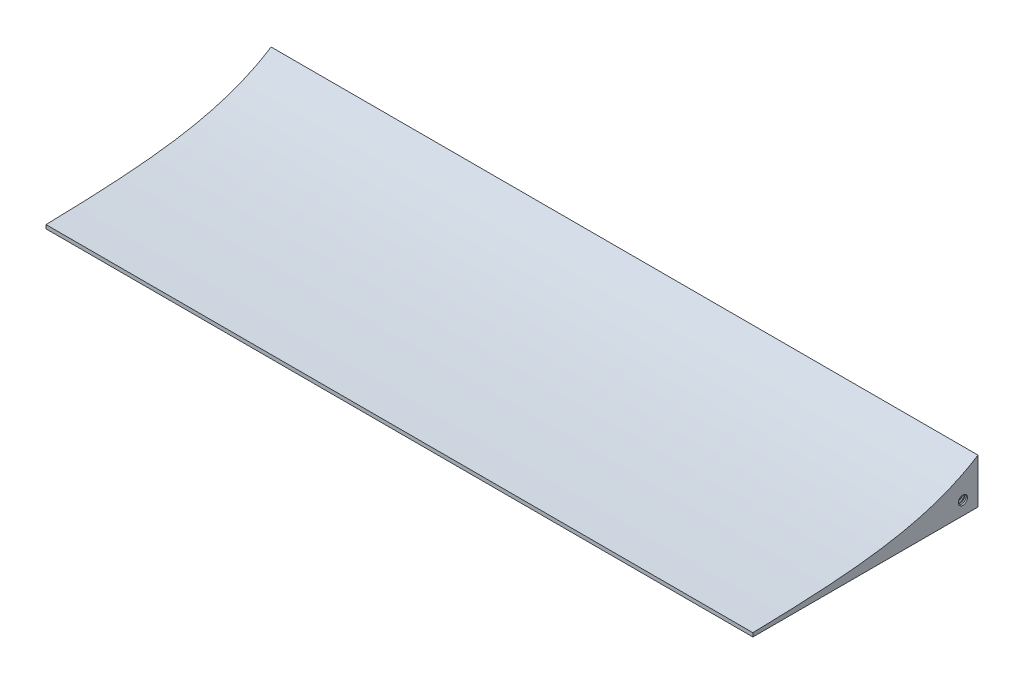
SolidWorks part; units mm, degrees
ref_plane "Front Plane" through (0, 0, 0) normal (0, 0, 1) x (1, 0, 0)
ref_plane "Top Plane" through (0, 0, 0) normal (0, 1, 0) x (1, 0, 0)
ref_plane "Right Plane" through (0, 0, 0) normal (1, 0, 0) x (0, 0, -1)
sketch "Sketch1" plane through (0, 0, 0) normal (0, 1, 0) x (1, 0, 0)
  line L1 (-199.39, -63.5) -> (199.39, -63.5)
  line L2 (-199.39, -63.5) -> (-199.39, 63.5)
  line L3 (-199.39, 63.5) -> (199.39, 63.5)
  line L4 (199.39, -63.5) -> (199.39, 63.5)
  line L5 (-199.39, -63.5) -> (199.39, 63.5) construction
  line L6 (-199.39, 63.5) -> (199.39, -63.5) construction
  point P0 (0, 0)
  dimension "D1" = 398.78
  dimension "D2" = 127
extrude "Boss-Extrude1" add sketch "Sketch1" along normal blind 25.4
sketch "Sketch2" plane through (199.39, 0, 0) normal (1, 0, 0) x (0, 0, -1)
  line L0 (-63.5, 0) -> (63.5, 0)
  line L1 (63.5, 0) -> (63.5, 25.4)
  line L2 (-63.5, 0) -> (-63.5, 2.1056)
  line L3 (-63.5, 25.4) -> (-63.5, 0) construction
  line L4 (63.5, 25.3699) -> (63.5, 0)
  line L5 (-63.5, 2.1056) -> (-63.5, 25.4)
  line L6 (-63.5, 25.4) -> (63.5, 25.4)
  spline S0 degree 4 poles (-152.4274, 1.3493) (-151.9263, 1.3506) (-151.0426, 1.3527) (-150.1628, 1.3532) (-145.5034, 1.3667) (-142.3632, 1.3703) (-131.1302, 1.4093) (-126.946, 1.4243) (-117.992, 1.4663) (-112.4222, 1.4979) (-106.4845, 1.5364) (-100.6598, 1.581) (-94.7897, 1.6332) (-88.9424, 1.694) (-83.0827, 1.7651) (-77.2301, 1.8481) (-69.9103, 1.9693) (-61.1294, 2.1471) (-50.885, 2.4138) (-39.1812, 2.8293) (-27.483, 3.3952) (-16.2855, 4.1336) (-5.595, 5.0798) (5.0653, 6.324) (15.6757, 7.9483) (26.0426, 10.062) (35.7881, 12.7) (44.4054, 15.6827) (51.8992, 18.868) (58.8522, 22.4356) (65.5095, 26.5301) (71.8193, 31.1423) (77.7584, 36.2511) (83.3048, 41.8087) (88.6296, 47.9588) (94.1337, 55.2543) (99.6609, 63.739) (105.095, 73.4301) (110.0607, 83.6631) (114.3675, 93.6944) (117.7696, 102.4989) (120.4463, 109.9927) (122.6536, 116.5709) (124.1141, 121.1398) (125.1524, 124.5039) (125.7907, 126.6144) (126.0535, 127.4898) (126.2686, 128.211) (126.5485, 129.1549) (126.8569, 130.2028) (127.0678, 130.9242) (127.3816, 132.0067) (127.6733, 133.0193) (128.0124, 134.2058) (128.3996, 135.5748) (128.8602, 137.2203) (129.3748, 139.0853) (130.0116, 141.4241) (130.7626, 144.2323) (131.6212, 147.5142) (132.579, 151.2704) (133.5146, 155.0325) (134.2002, 157.8579) (134.6505, 159.7432) (134.874, 160.6862) knots 0 0 0 0 0 0.004219 0.008439 0.016877 0.033754 0.067509 0.083072 0.098635 0.114198 0.129761 0.145324 0.160887 0.17645 0.192013 0.207577 0.22314 0.254266 0.285392 0.316518 0.347644 0.378771 0.404687 0.430603 0.461729 0.492855 0.517102 0.537852 0.558603 0.579354 0.600105 0.620855 0.641607 0.662555 0.683503 0.707273 0.738696 0.770119 0.801542 0.828135 0.854728 0.87044 0.886151 0.901863 0.905791 0.907755 0.909719 0.911683 0.913647 0.917575 0.92015 0.922726 0.925302 0.927878 0.933029 0.938181 0.943333 0.948484 0.958787 0.96909 0.979394 0.989697 1 1 1 1 1 construction
  spline S1 degree 4 poles (-127, 1.4256) (-125.7556, 1.4307) (-123.1889, 1.4419) (-117.992, 1.4663) (-112.4222, 1.4979) (-106.4845, 1.5364) (-100.6598, 1.581) (-94.7897, 1.6332) (-88.9424, 1.694) (-83.0827, 1.7651) (-77.2301, 1.8481) (-69.9103, 1.9693) (-61.1294, 2.1471) (-50.885, 2.4138) (-39.1812, 2.8293) (-27.483, 3.3952) (-16.2855, 4.1336) (-5.595, 5.0798) (5.0653, 6.324) (15.6757, 7.9483) (26.0426, 10.062) (35.7881, 12.7) (44.4054, 15.6827) (51.8992, 18.868) (58.8522, 22.4356) (65.5095, 26.5301) (71.8193, 31.1423) (77.7584, 36.2511) (83.3048, 41.8087) (88.6296, 47.9588) (94.1337, 55.2543) (99.6609, 63.739) (105.095, 73.4301) (110.0607, 83.6631) (114.3675, 93.6944) (117.7696, 102.4989) (120.4463, 109.9927) (122.6536, 116.5709) (124.1141, 121.1398) (125.1524, 124.5039) (125.7907, 126.6144) (126.0535, 127.4898) (126.2686, 128.211) (126.5485, 129.1549) (126.7807, 129.9441) (126.912, 130.3919) (127, 130.6934) knots 0.067509 0.067509 0.067509 0.067509 0.067509 0.083072 0.098635 0.114198 0.129761 0.145324 0.160887 0.17645 0.192013 0.207577 0.22314 0.254266 0.285392 0.316518 0.347644 0.378771 0.404687 0.430603 0.461729 0.492855 0.517102 0.537852 0.558603 0.579354 0.600105 0.620855 0.641607 0.662555 0.683503 0.707273 0.738696 0.770119 0.801542 0.828135 0.854728 0.87044 0.886151 0.901863 0.905791 0.907755 0.909719 0.911683 0.913647 0.917575 0.917575 0.917575 0.917575 0.917575
  line M3 (63.5, 25.4) -> (-63.5, 25.4)
  line M4 (-63.5, 25.4) -> (-63.5, 0)
extrude "Cut-Extrude1" cut sketch "Sketch2" against normal through all contours S1 L1 M4 M3 region at (199.39, 15.6798, 12.1776)
sketch "Sketch3" plane through (0, 0, 0) normal (0, -1, 0) x (1, 0, 0)
  line L0 (-199.39, -63.5) -> (-199.39, 63.5) construction
  line L1 (199.39, -63.5) -> (-199.39, -63.5) construction
  circle A0 centre (-179.07, -31.75) radius 10
  circle A3 centre (-179.07, -6.35) radius 10
  circle A5 centre (-128.27, -6.35) radius 10
  circle A7 centre (-77.47, -6.35) radius 10
  circle A9 centre (-26.67, -6.35) radius 10
  circle A11 centre (24.13, -6.35) radius 10
  circle A13 centre (-128.27, -31.75) radius 10
  circle A14 centre (-77.47, -31.75) radius 10
  circle A15 centre (-26.67, -31.75) radius 10
  circle A16 centre (24.13, -31.75) radius 10
  circle A22 centre (74.93, -31.75) radius 10
  circle A23 centre (74.93, -6.35) radius 10
  circle A25 centre (125.73, -31.75) radius 10
  circle A26 centre (125.73, -6.35) radius 10
  circle A28 centre (176.53, -31.75) radius 10
  circle A29 centre (176.53, -6.35) radius 10
  dimension "D1" = 20
  dimension "D2" = 20.32
  dimension "D3" = 2
  dimension "D4" = 31.75
  dimension "D6" = 25.4
  dimension "D5" = 8
extrude "Cut-Extrude2" cut sketch "Sketch3" against normal blind 5
sketch "Sketch4" plane through (0, 0, 0) normal (0, -1, 0) x (1, 0, 0)
  line L0 (-199.39, -63.5) -> (-199.39, 63.5) construction
  line L1 (199.39, -63.5) -> (-199.39, -63.5) construction
  circle A0 centre (74.93, -31.75) radius 10
  circle A1 centre (125.73, -31.75) radius 10
  circle A2 centre (-179.07, -31.75) radius 10
  circle A3 centre (-128.27, -31.75) radius 10
  circle A4 centre (-77.47, -31.75) radius 10
  circle A5 centre (-26.67, -31.75) radius 10
  circle A6 centre (24.13, -31.75) radius 10
  circle A7 centre (-128.27, -6.35) radius 10
  circle A8 centre (-77.47, -6.35) radius 10
  circle A9 centre (-26.67, -6.35) radius 10
  circle A10 centre (24.13, -6.35) radius 10
  circle A11 centre (-128.27, 19.05) radius 10
  circle A12 centre (-77.47, 19.05) radius 10
  circle A13 centre (-26.67, 19.05) radius 10
  circle A14 centre (24.13, 19.05) radius 10
  circle A15 centre (-179.07, -6.35) radius 10
  circle A16 centre (-179.07, 19.05) radius 10
  circle A17 centre (176.53, -31.75) radius 10
  circle A18 centre (74.93, -6.35) radius 10
  circle A19 centre (125.73, -6.35) radius 10
  circle A20 centre (176.53, -6.35) radius 10
  circle A21 centre (74.93, 19.05) radius 10
  circle A22 centre (125.73, 19.05) radius 10
  circle A23 centre (176.53, 19.05) radius 10
  ellipse E0 centre (-179.07, -31.75) end of major axis (-169.07, -31.75) minor radius 7.7543
  ellipse E1 centre (-128.27, -31.75) end of major axis (-138.27, -31.75) minor radius 7.7543
  ellipse E2 centre (-77.47, -31.75) end of major axis (-67.47, -31.75) minor radius 7.7543
  ellipse E3 centre (-26.67, -31.75) end of major axis (-16.67, -31.75) minor radius 7.7543
  ellipse E4 centre (24.13, -31.75) end of major axis (34.13, -31.75) minor radius 7.7543
  ellipse E5 centre (74.93, -31.75) end of major axis (84.93, -31.75) minor radius 7.7543
  ellipse E6 centre (125.73, -31.75) end of major axis (135.73, -31.75) minor radius 7.7543
  ellipse E7 centre (176.53, -31.75) end of major axis (186.53, -31.75) minor radius 7.7543
  ellipse E8 centre (-128.27, -6.35) end of major axis (-118.27, -6.35) minor radius 7.7543
  ellipse E9 centre (-77.47, -6.35) end of major axis (-67.47, -6.35) minor radius 7.7543
  ellipse E10 centre (-26.67, -6.35) end of major axis (-16.67, -6.35) minor radius 7.7543
  ellipse E11 centre (24.13, -6.35) end of major axis (34.13, -6.35) minor radius 7.7543
  ellipse E12 centre (74.93, -6.35) end of major axis (84.93, -6.35) minor radius 7.7543
  ellipse E13 centre (125.73, -6.35) end of major axis (135.73, -6.35) minor radius 7.7543
  ellipse E14 centre (176.53, -6.35) end of major axis (186.53, -6.35) minor radius 7.7543
  ellipse E15 centre (-128.27, 19.05) end of major axis (-118.27, 19.05) minor radius 7.7543
  ellipse E16 centre (-77.47, 19.05) end of major axis (-67.47, 19.05) minor radius 7.7543
  ellipse E17 centre (-26.67, 19.05) end of major axis (-16.67, 19.05) minor radius 7.7543
  ellipse E18 centre (24.13, 19.05) end of major axis (34.13, 19.05) minor radius 7.7543
  ellipse E19 centre (74.93, 19.05) end of major axis (84.93, 19.05) minor radius 7.7543
  ellipse E20 centre (125.73, 19.05) end of major axis (135.73, 19.05) minor radius 7.7543
  ellipse E21 centre (176.53, 19.05) end of major axis (186.53, 19.05) minor radius 7.7543
  ellipse E22 centre (-179.07, -6.35) end of major axis (-169.07, -6.35) minor radius 7.7543
  ellipse E23 centre (-179.07, 19.05) end of major axis (-169.07, 19.05) minor radius 7.7543
  circle M12 centre (-179.07, -6.35) radius 10
  circle M14 centre (-128.27, -6.35) radius 10
  circle M16 centre (-77.47, -6.35) radius 10
  circle M18 centre (-26.67, -6.35) radius 10
  circle M20 centre (24.13, -31.75) radius 10
  circle M21 centre (-26.67, -31.75) radius 10
  circle M22 centre (-77.47, -31.75) radius 10
  circle M23 centre (-128.27, -31.75) radius 10
  circle M25 centre (24.13, -6.35) radius 10
  circle M26 centre (-179.07, -31.75) radius 10
  circle M97 centre (74.93, -31.75) radius 10
  circle M98 centre (74.93, -6.35) radius 10
  circle M104 centre (125.73, -6.35) radius 10
  circle M105 centre (125.73, -31.75) radius 10
  circle M107 centre (176.53, -31.75) radius 10
  circle M108 centre (176.53, -6.35) radius 10
  dimension "D1" = 31.75
  dimension "D2" = 20.32
  dimension "D8" = 25.4
  dimension "D5" = 8
  dimension "D6" = 3
  dimension "D3" = 8
  dimension "D4" = 3
extrude "Boss-Extrude2" add sketch "Sketch4" against normal blind 1.27 contours A15 | A15 | A21 A3 | A21 A3 | A7 | A7 | A8 | A8 | E0 A4 | E0 A4 | A9 | A9 | A5 | A5 | A6 | A10 | E22 M12 | E23 A16 | E15 A11 | E8 M14 | E1 M23 | E16 A12 | E1 A3 | E0 M26 | E9 A8 | E2 A4 | E2 M22 | E17 A13 | E17 A13 | E10 M18 | E3 M21 | E3 A5 | E4 M20 | E11 M25 | E18 A14 | E8 A7 | E0 A2 | E9 M16 | E12 M98 | E19 A21 | E12 A18 | E5 M97 | E5 A0 | E19 A21 | E20 A22 | E13 M104 | E20 A22 | E13 A19 | E6 M105 | E6 A1 | E21 A23 | E21 A23 | E14 M108 | E14 A20 | E7 M107 | E7 A17 | E18 region at (74.93, 0, -23.7721) region at (74.93, 0, -41.5264) region at (125.73, 0, -23.7721) region at (125.73, 0, -41.5264) region at (-179.07, 0, -23.7721) region at (-179.07, 0, -41.5264) region at (-128.27, 0, -23.7721) region at (-128.27, 0, -41.5264) region at (-77.47, 0, -23.7721) region at (-77.47, 0, -41.5264) region at (-26.67, 0, -23.7721) region at (-26.67, 0, -41.5264) region at (24.13, 0, -23.7721) region at (24.13, 0, -41.5264) region at (-128.27, 0, 1.6279) region at (-128.27, 0, -16.1264) region at (-77.47, 0, 1.6279) region at (-77.47, 0, -16.1264) region at (-26.67, 0, 1.6279) region at (-26.67, 0, -16.1264) region at (24.13, 0, 1.6279) region at (24.13, 0, -16.1264) region at (-128.27, 0, 27.0279) region at (-77.47, 0, 27.0279) region at (-26.67, 0, 27.0279) region at (-26.67, 0, 9.2736) region at (24.13, 0, 9.2736) region at (-179.07, 0, 1.6279) region at (-179.07, 0, -16.1264) region at (-179.07, 0, 27.0279) region at (176.53, 0, -23.7721) region at (176.53, 0, -41.5264) region at (74.93, 0, 1.6279) region at (74.93, 0, -16.1264) region at (125.73, 0, 1.6279) region at (125.73, 0, -16.1264) region at (176.53, 0, 1.6279) region at (176.53, 0, -16.1264) region at (74.93, 0, 27.0279) region at (74.93, 0, 9.2736) region at (125.73, 0, 27.0279) region at (125.73, 0, 9.2736) region at (176.53, 0, 27.0279) region at (176.53, 0, 9.2736)
sketch "Sketch5" plane through (-199.39, 0, 0) normal (-1, 0, 0) x (0, 0, 1)
  line L1 (-63.5, 0) -> (63.5, 0) construction
  point P0 (-54.9744, 7.62)
  dimension "D1" = 7.62
hole_wizard "#7 (0.201) Diameter Hole1" positions "Sketch6" profile "Sketch7" hole size "#7" standard "ANSI Inch"
sketch "Sketch6" plane through (-199.39, 0, 0) normal (-1, 0, 0) x (0, 0, 1)
  point P0 (-54.9744, 7.62)
  point P7 (-54.9744, 7.62)
sketch "Sketch7" plane through (-199.39, 7.62, -54.9744) normal (0, 1, 0) x (0, 0, 1)
  line L0 (0, 0) -> (0, 39.6338)
  line L1 (0, 39.6338) -> (2.5527, 38.1)
  line L2 (2.5527, 38.1) -> (2.5527, 0)
  line L5 (2.5527, 0) -> (0, 0)
  line L10 (0, 39.6338) -> (-2.5527, 38.1) construction
  line L11 (0, -6.35) -> (0, 107.95) construction
  dimension "Hole Dia." = 5.1054
  dimension "Hole Depth" = 38.1
  dimension "Drill Angle" = 118
sketch "Sketch8" plane through (199.39, 0, 0) normal (1, 0, 0) x (0, 0, -1)
  line L0 (63.5, 25.3699) -> (63.5, 0) construction
  line L1 (-63.5, 0) -> (63.5, 0) construction
  point P0 (54.864, 7.62)
  dimension "D1" = 8.636
  dimension "D2" = 7.62
hole_wizard "#7 (0.201) Diameter Hole3" positions "Sketch11" profile "Sketch12" hole size "#7" standard "ANSI Inch"
sketch "Sketch11" plane through (199.39, 0, 0) normal (1, 0, 0) x (0, 0, -1)
  point P0 (54.9744, 7.62)
  point P4 (54.9744, 7.62)
sketch "Sketch12" plane through (199.39, 7.62, -54.9744) normal (0, 1, 0) x (0, 0, -1)
  line L0 (0, 0) -> (0, 39.6338)
  line L1 (0, 39.6338) -> (2.5527, 38.1)
  line L2 (2.5527, 38.1) -> (2.5527, 0)
  line L5 (2.5527, 0) -> (0, 0)
  line L10 (0, 39.6338) -> (-2.5527, 38.1) construction
  line L11 (0, -6.35) -> (0, 107.95) construction
  dimension "Hole Dia." = 5.1054
  dimension "Hole Depth" = 38.1
  dimension "Drill Angle" = 118
thread "Thread1" pitch 1.27 method cut profile "Thread Profile1" start angle 0, offset 0, length 25.4, pitch 1.27, diameter 5.1054
ref_plane "Plane1" through (199.39, 7.62, -52.4217) normal (0, -1, 0) x (0, 0, 1)
sketch "Thread Profile1" plane through (199.39, 7.62, -52.4217) normal (0, -1, 0) x (0, 0, 1)
  line L0 (0, 0) -> (0, 1.27) construction
  line L1 (0, 0) -> (0.6874, 0.3969)
  line L2 (0.6874, 0.3969) -> (0.6874, 0.5556)
  line L3 (0.6874, 0.5556) -> (0, 0.9525)
  line L4 (0.6874, 0.4762) -> (0, 0.4762) construction
  line L11 (0, 0) -> (0, 0.9525)
  point P2 (0, 0)
  dimension "Pitch" = 1.27
  dimension "Profile_Angle" = 60
  dimension "Profile_Land" = 0.1588
  dimension "Profile_Height" = 0.6874
thread "Thread2" pitch 1.27 method cut profile "Thread Profile2" start angle 0, offset 0, length 25.4, pitch 1.27, diameter 5.1054
ref_plane "Plane2" through (-199.39, 7.62, -57.5271) normal (0, -1, 0) x (0, 0, -1)
sketch "Thread Profile2" plane through (-199.39, 7.62, -57.5271) normal (0, -1, 0) x (0, 0, -1)
  line L0 (0, 0) -> (0, 1.27) construction
  line L1 (0, 0) -> (0.6874, 0.3969)
  line L2 (0.6874, 0.3969) -> (0.6874, 0.5556)
  line L3 (0.6874, 0.5556) -> (0, 0.9525)
  line L4 (0.6874, 0.4762) -> (0, 0.4762) construction
  line L11 (0, 0) -> (0, 0.9525)
  point P2 (0, 0)
  dimension "Pitch" = 1.27
  dimension "Profile_Angle" = 60
  dimension "Profile_Land" = 0.1588
  dimension "Profile_Height" = 0.6874
